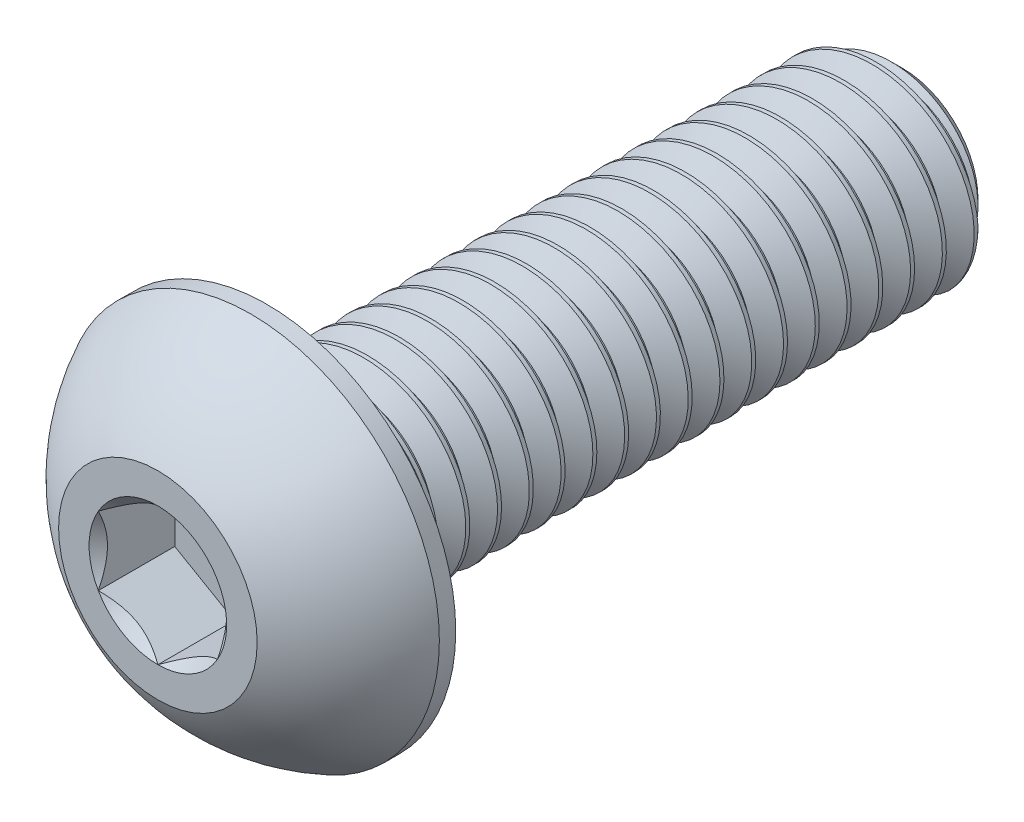
SolidWorks part; units mm, degrees
ref_plane "Front" through (0, 0, 0) normal (0, 0, 1) x (1, 0, 0)
ref_plane "Top" through (0, 0, 0) normal (0, 1, 0) x (1, 0, 0)
ref_plane "Right" through (0, 0, 0) normal (1, 0, 0) x (0, 0, -1)
sketch "Sketch1" plane through (0, 0, 0) normal (1, 0, 0) x (0, 0, -1)
  line L2 (2.75, 2.5) -> (18.75, 2.5)
  line L3 (18.75, 2.5) -> (18.75, 0)
  line L4 (18.75, 0) -> (2.75, 0)
  line L6 (2.3375, 4.75) -> (2.75, 4.75) construction
  line L7 (18.75, 2.5) -> (18.75, -2.5) construction
  line L8 (0, 0) -> (2.75, 0) construction
  line L9 (2.75, 4.75) -> (2.75, -4.75) construction
  line L11 (2.75, 2.5) -> (2.75, 0)
  line L13 (0, 1.5) -> (0, -1.5) construction
  line L14 (0, 1.5) -> (0, 2.5) construction
  arc A3 (0, 2.5) -> (2.3375, 4.75) centre (4.6581, 0) cw construction
  dimension "D1" = 0.4125
  dimension "Head Ht" = 2.75
  dimension "Head Dia" = 9.5
  dimension "Dia" = 5
  dimension "Lg" = 16
  dimension "Hex" = 3
revolve "Revolve1" add sketch "Sketch1" angle 360 mid plane about L4
sketch "Sketch3" plane through (0, 0, -18.75) normal (0, 0, -1) x (-1, 0, 0)
  circle A0 centre (0, 0) radius 2.5
curve "Helix/Spiral1" pitch 0.8 height 16.8 radius 2.5 centre (0, 0, -18.75) axis (0, 0, 1) start towards (0, 1, 0)
sketch "Sketch2" plane through (0, 0, 0) normal (1, 0, 0) x (0, 0, -1)
  line L0 (18.75, 2.5) -> (19.45, 2.5)
  line L1 (19.45, 2.5) -> (19.15, 1.9804)
  line L2 (19.15, 1.9804) -> (19.05, 1.9804)
  line L3 (19.05, 1.9804) -> (18.75, 2.5)
  line L4 (18.9, 2.2402) -> (19.3, 2.2402) construction
  dimension "D1" = 60
  dimension "D2" = 0.1
  dimension "D3" = 0.4
chamfer "Chamfer1" distance 0.6 angle 45 1 edges at (0, 2.5, -18.75)
sweep "Cut-Sweep1" cut profiles "Sketch2" path "Helix/Spiral1" align with end faces yes
sketch "Sketch7" plane through (0, 0, 0) normal (1, 0, 0) x (0, 0, -1)
  line L6 (2.3375, 4.75) -> (2.75, 4.75) construction
  line L8 (0, 0) -> (2.75, 0) construction
  line L11 (2.75, 4.75) -> (2.75, -4.75) construction
  line L12 (2.3375, 4.75) -> (2.75, 4.75)
  line L13 (0, 0) -> (2.75, 0)
  line L14 (0, 1.5) -> (0, -1.5) construction
  line L15 (2.75, 4.75) -> (2.75, 0)
  line L16 (0, 2.5) -> (0, 0)
  arc A2 (2.3375, 4.75) -> (0, 2.5) centre (4.6581, 0) ccw construction
  arc A3 (2.3375, 4.75) -> (0, 2.5) centre (4.6581, 0) ccw
revolve "Revolve2" add sketch "Sketch7" angle 360 mid plane about L13
sketch "Sketch5" plane through (0, 0, 0) normal (0, 0, 1) x (1, 0, 0)
  line L1 (1.5, -0.866) -> (1.5, 0.866)
  line L2 (1.5, 0.866) -> (0, 1.7321)
  line L3 (0, 1.7321) -> (-1.5, 0.866)
  line L4 (-1.5, 0.866) -> (-1.5, -0.866)
  line L5 (-1.5, -0.866) -> (0, -1.7321)
  line L6 (0, -1.7321) -> (1.5, -0.866)
  circle A0 centre (0, 0) radius 1.5 construction
extrude "Cut-Extrude2" cut sketch "Sketch5" against normal blind 1.925
sketch "Sketch6" plane through (0, 0, 0) normal (0, 0, 1) x (1, 0, 0)
  circle A0 centre (0, 0) radius 1.7321
extrude "Cut-Extrude3" cut sketch "Sketch6" against normal blind 1.925 draft 45
sketch "Sketch9" [suppressed] plane through (0, 0, -2.75) normal (0, 0, 1) x (1, 0, 0)
  circle A2 centre (0, 0) radius 2.5
extrude "Boss-Extrude2" [suppressed] add sketch "Sketch9" against normal offset from surface (13 mm away) 20 up to face at (0, 1.9, -18.75)
sketch "Sketch10" plane through (0, 0, 0) normal (1, 0, 0) x (0, 0, -1)
  line L0 (18.75, 2.5) -> (18.75, -2.5) construction
  point P0 (17.55, -2.5)
  dimension "D1" = 1.2
equation "\"D3@Helix/Spiral1\" = \"Lg@Sketch1\" + \"D4@Helix/Spiral1\""
equation "\"D2@Sketch2\" = \"D4@Helix/Spiral1\" * .125"
equation "\"D3@Sketch2\" = \"D4@Helix/Spiral1\" * .5"
equation "\"D1@Chamfer1\" = \"D4@Helix/Spiral1\" * .75"
equation "\"D1@Cut-Extrude2\" = \"Head Ht@Sketch1\" * .7"
equation "\"D1@Sketch1\" = \"Head Ht@Sketch1\" * .15"
equation "\"D1@Sketch10\" = \"D4@Helix/Spiral1\" * 1.5"
equation "\"D1@Cut-Extrude3\" = \"D1@Cut-Extrude2\""
